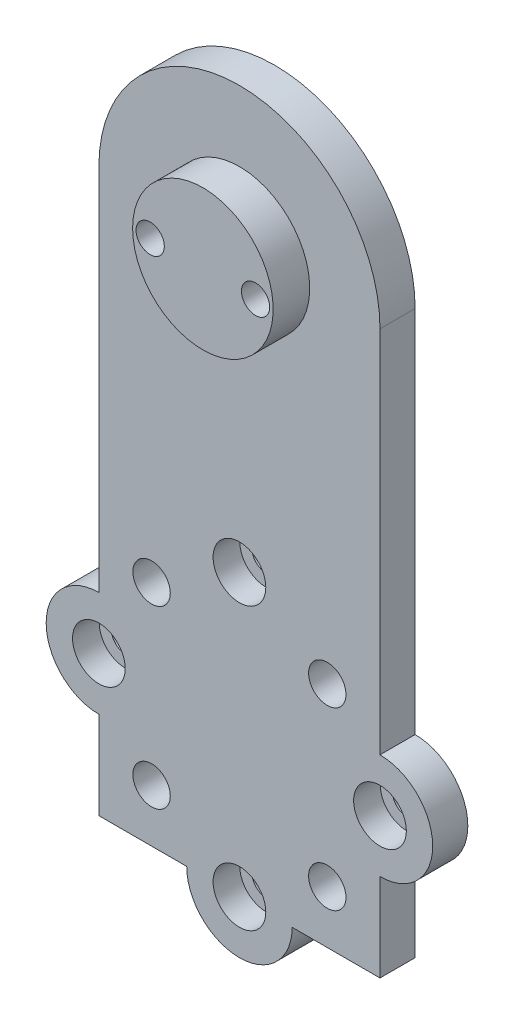
SolidWorks part; units mm, degrees
material "6061 Alloy"
ref_plane "Front Plane" through (0, 0, 0) normal (0, 0, 1) x (1, 0, 0)
ref_plane "Top Plane" through (0, 0, 0) normal (0, 1, 0) x (1, 0, 0)
ref_plane "Right Plane" through (0, 0, 0) normal (1, 0, 0) x (0, 0, -1)
sketch "Sketch1" plane through (0, 0, 0) normal (0, 0, 1) x (1, 0, 0)
  line L1 (0, 0) -> (15.875, 0)
  line L14 (0, 0) -> (0, 15.875)
  line L15 (50.8, 101.6) -> (50.8, 34.925)
  line L16 (0, 34.925) -> (0, 101.6)
  line L17 (50.8, 15.875) -> (50.8, 0)
  line L18 (34.925, 0) -> (50.8, 0)
  arc A0 (50.8, 101.6) -> (0, 101.6) centre (25.4, 101.6) ccw
  circle A4 centre (41.275, 9.525) radius 3.3782
  circle A5 centre (9.525, 9.525) radius 3.3782
  circle A6 centre (9.525, 41.275) radius 3.3782
  circle A7 centre (41.275, 41.275) radius 3.3782
  arc A8 (50.8, 15.875) -> (50.8, 34.925) centre (50.8, 25.4) ccw
  arc A9 (0, 15.875) -> (0, 34.925) centre (0, 25.4) cw
  arc A10 (34.925, 0) -> (15.875, 0) centre (25.4, 0) cw
  dimension "D1" = 101.6
  dimension "D7" = 6.7564
  dimension "D8" = 9.525
  dimension "D9" = 15.875
  dimension "D11" = 25.4
  dimension "D2" = 31.75
  dimension "D3" = 9.525
  dimension "D4" = 31.75
  dimension "D5" = 50.8
  dimension "D6" = 9.525
  dimension "D10" = 15.875
extrude "Boss-Extrude1" add sketch "Sketch1" along normal blind 6.35
sketch "Sketch2" plane through (0, 0, 6.35) normal (0, 0, 1) x (1, 0, 0)
  line L0 (0, 101.6) -> (50.8, 101.6) construction
  line L1 (25.4, 127) -> (25.4, 101.6) construction
  arc A0 (50.8, 101.6) -> (0, 101.6) centre (25.4, 101.6) ccw construction
  circle A1 centre (25.4, 101.6) radius 12.7
  dimension "D1" = 25.4
extrude "Boss-Extrude2" add sketch "Sketch2" along normal blind 6.604
hole_wizard "CBORE for #10 Socket Head Cap Screw1" positions "Sketch3" profile "Sketch4" counterbore size "#10" standard "ANSI Inch" end condition through all
sketch "Sketch3" plane through (0, 0, 6.35) normal (0, 0, 1) x (1, 0, 0)
  line L0 (34.925, 0) -> (50.8, 0) construction
  circle A0 centre (25.4, 25.4) radius 25.4 construction
  point P0 (0, 25.4)
  point P3 (50.8, 25.4)
  point P6 (25.4, 0)
  point P14 (25.4, 50.8)
  dimension "D1" = 50.8
  dimension "D2" = 25.4
sketch "Sketch4" plane through (0, 25.4, 6.35) normal (1, 0, 0) x (0, -1, 0)
  line L0 (0, 0) -> (0, 6.35)
  line L1 (0, 6.35) -> (2.5527, 6.35)
  line L3 (2.5527, 6.35) -> (2.5527, 4.826)
  line L4 (2.5527, 4.826) -> (4.7625, 4.826)
  line L5 (4.7625, 4.826) -> (4.7625, 0)
  line L7 (4.7625, 0) -> (0, 0)
  line L11 (0, -6.35) -> (0, 107.95) construction
  dimension "Thru Hole Dia." = 5.1054
  dimension "Thru Hole Depth" = 6.35
  dimension "C'Bore Dia." = 9.525
  dimension "C'Bore Depth" = 4.826
hole_wizard "1/4-20 Tapped Hole2" positions "Sketch8" profile "Sketch9" tap size "1/4-20" standard "ANSI Inch" end condition through all
sketch "Sketch8" plane through (0, 0, 12.954) normal (0, 0, 1) x (1, 0, 0)
  line L0 (12.7, 101.6) -> (38.1, 101.6) construction
  line L2 (25.4, 114.3) -> (25.4, 88.9) construction
  circle A0 centre (25.4, 101.6) radius 12.7 construction
  circle A1 centre (25.4, 101.6) radius 12.7 construction
  point P0 (15.875, 101.6)
  point P2 (34.925, 101.6)
  point P18 (15.9639, 101.6)
  dimension "D1" = 19.05
  dimension "D2" = 3.175
  dimension "D3" = 3.175
sketch "Sketch9" plane through (15.875, 101.6, 12.954) normal (1, 0, 0) x (0, -1, 0)
  line L0 (0, 0) -> (0, 12.954)
  line L1 (0, 12.954) -> (2.5527, 12.954)
  line L2 (2.5527, 12.954) -> (2.5527, 0)
  line L5 (2.5527, 0) -> (0, 0)
  line L11 (0, -6.35) -> (0, 107.95) construction
  dimension "Thru Tap Drill Dia." = 5.1054
  dimension "Thru Tap Drill Depth" = 12.954
cosmetic thread "Hole Thread3" parameters "D2"=6.35
cosmetic thread "Hole Thread4" parameters "D2"=6.35
